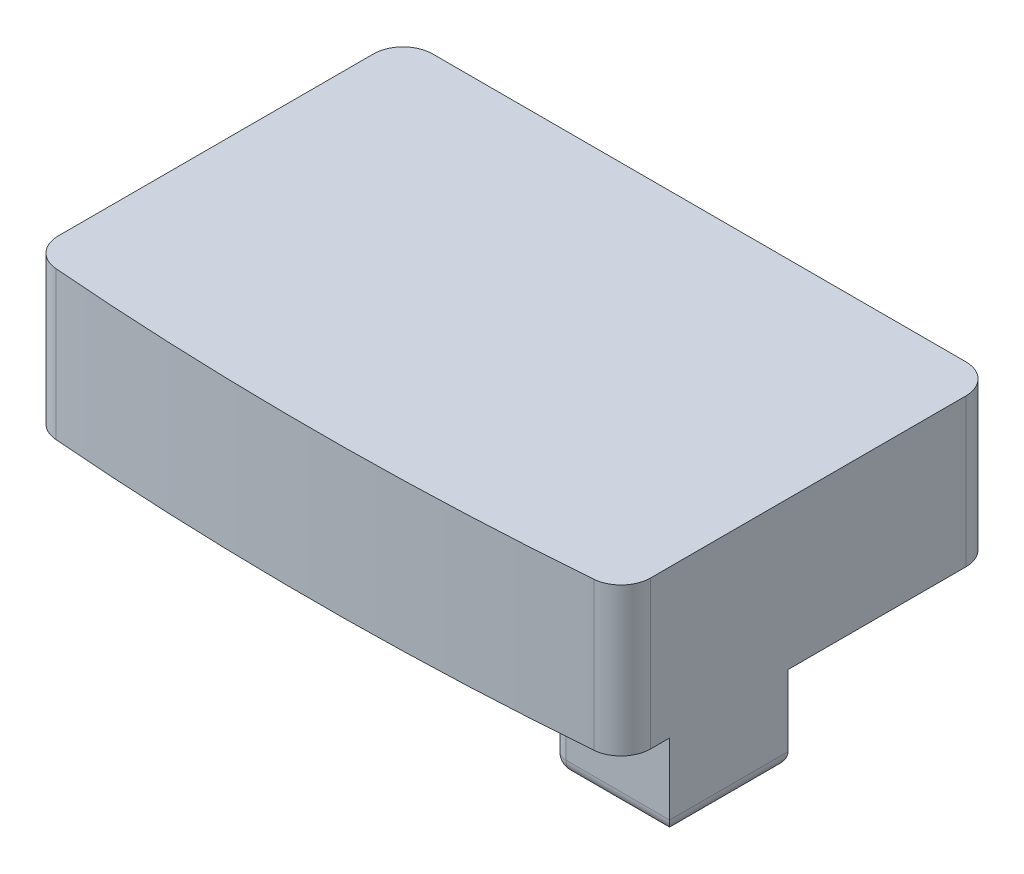
SolidWorks part; units mm, degrees
material "6061 Alloy"
ref_plane "Front Plane" through (0, 0, 0) normal (0, 0, 1) x (1, 0, 0)
ref_plane "Top Plane" through (0, 0, 0) normal (0, 1, 0) x (1, 0, 0)
ref_plane "Right Plane" through (0, 0, 0) normal (1, 0, 0) x (0, 0, -1)
sketch "Sketch1" plane through (0, 0, 0) normal (0, 1, 0) x (1, 0, 0)
  line L0 (10.5, 0) -> (10.5, 114) construction
  line L2 (0.5, 0.4394) -> (0.5, 13)
  line L3 (0.5, 13) -> (20.5, 13)
  line L4 (20.5, 0.4394) -> (20.5, 13)
  line L5 (10.5, 114) -> (10.5, 4) construction
  circle A0 centre (4.5, 9) radius 1.5
  circle A1 centre (16.5, 9) radius 1.5
  arc A7 (0.5, 0.4394) -> (20.5, 0.4394) centre (10.5, 114) ccw
  dimension "D3" = 3
  dimension "D4" = 3
  dimension "D1" = 20
  dimension "D2" = 10
  dimension "D5" = 4
  dimension "D6" = 4
  dimension "D7" = 4
  dimension "D8" = 9
  dimension "D9" = 13
  dimension "D10" = 110
extrude "Boss-Extrude1" add sketch "Sketch1" along normal blind 5 contours L3 L4 A7 L2
fillet "Fillet1" radius 1 4 edges at (20.5, 2.5, -13) (0.5, 2.5, -13) (20.5, 2.5, -0.4394) (0.5, 2.5, -0.4394)
sketch "Sketch2" plane through (0, 0, 0) normal (0, -1, 0) x (1, 0, 0)
  line L1 (0.5, -1.359) -> (0.5, -12) construction
  line L2 (20.5, -1.359) -> (20.5, -12) construction
  line L3 (1.5, -13) -> (19.5, -13) construction
  circle A0 centre (5.5, -10) radius 0.7835
  circle A1 centre (15.5, -10) radius 0.7835
  point P4 (0, 0)
  dimension "D1" = 5
  dimension "D2" = 5
  dimension "D4" = 1.567
  dimension "D3" = 3
extrude "Cut-Extrude1" cut sketch "Sketch2" against normal blind 4 contours A0 | A1
sketch "Sketch3" plane through (20.5, 0, 0) normal (1, 0, 0) x (0, 0, -1)
  line L0 (1.359, 0) -> (12, 0) construction
  line L1 (2, 0) -> (6, 0)
  line L2 (2, 0) -> (2, -2.9)
  line L3 (2, -2.9) -> (6, -2.9)
  line L4 (6, 0) -> (6, -2.9)
  line L5 (13, 5) -> (13, 0) construction
  dimension "D1" = 7
  dimension "D2" = 4
  dimension "D3" = 2.9
extrude "Boss-Extrude2" add sketch "Sketch3" against normal blind 4
fillet "Fillet2" radius 0.5 6 edges at (18.5, -2.9, -6) (16.5, -2.9, -4) (18.5, -2.9, -2) (20.5, -2.9, -4) (16.5, -1.45, -2) (16.5, -1.45, -6)
